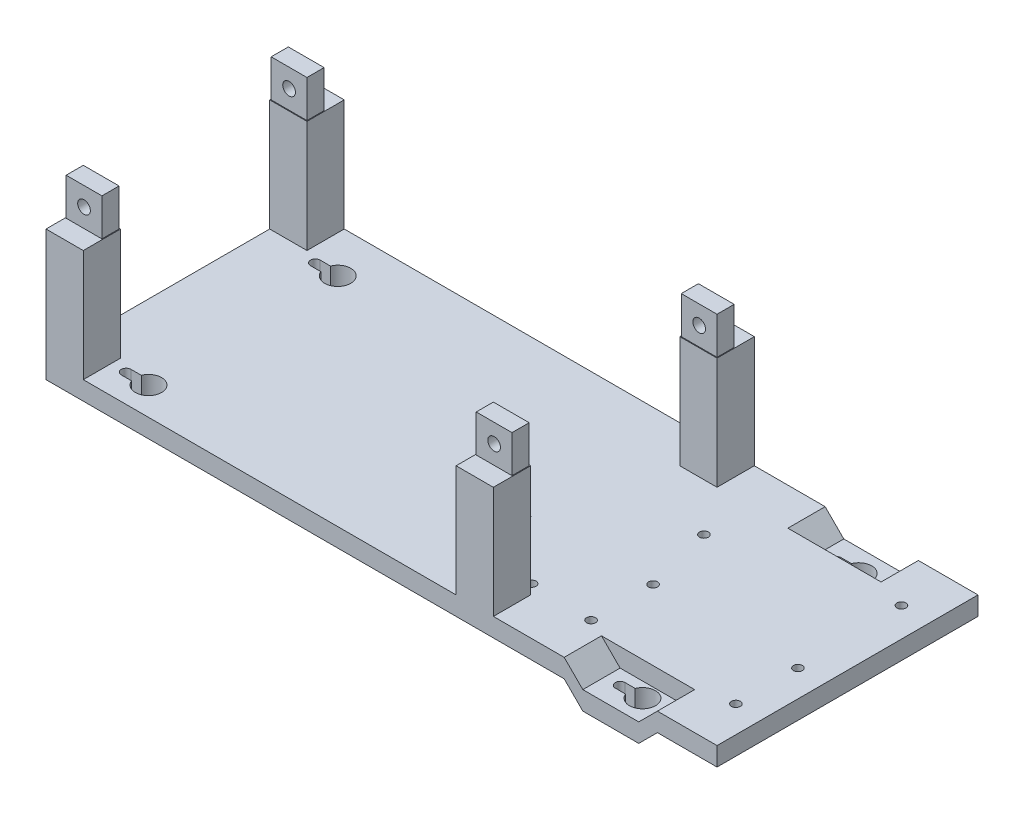
SolidWorks part; units mm, degrees
ref_plane "Front Plane" through (0, 0, 0) normal (0, 0, 1) x (1, 0, 0)
ref_plane "Top Plane" through (0, 0, 0) normal (0, 1, 0) x (1, 0, 0)
ref_plane "Right Plane" through (0, 0, 0) normal (1, 0, 0) x (0, 0, -1)
sketch "Sketch1" plane through (0, 0, 0) normal (0, 1, 0) x (1, 0, 0)
  line L1 (-90, -35) -> (90, -35)
  line L2 (-90, -35) -> (-90, 35)
  line L3 (-90, 35) -> (90, 35)
  line L4 (90, -35) -> (90, 35)
  line L5 (-90, -35) -> (90, 35) construction
  line L6 (-90, 35) -> (90, -35) construction
  point P0 (0, 0)
  dimension "D1" = 180
  dimension "D2" = 70
extrude "Boss-Extrude1" add sketch "Sketch1" along normal blind 5
sketch "Sketch3" plane through (0, 5, 0) normal (0, 1, 0) x (1, 0, 0)
  line L0 (90, 35) -> (-90, 35) construction
  line L1 (69, 35) -> (54, 35)
  line L2 (69, 35) -> (69, 25)
  line L3 (69, 25) -> (54, 25)
  line L4 (54, 35) -> (54, 25)
  line L5 (-90, -35) -> (90, -35) construction
  line L6 (69, -35) -> (54, -35)
  line L7 (69, -35) -> (69, -25)
  line L8 (69, -25) -> (54, -25)
  line L9 (54, -35) -> (54, -25)
  line L10 (90, -35) -> (90, 35) construction
  dimension "D1" = 10
  dimension "D2" = 15
  dimension "D3" = 21
extrude "Cut-Extrude1" cut sketch "Sketch3" against normal blind 6
chamfer "Chamfer2" distance 5 angle 45 4 edges at (54, 5, 30) (69, 5, 30) (69, 5, -30) (54, 5, -30)
sketch "Sketch5" plane through (0, 0, 0) normal (0, -1, 0) x (1, 0, 0)
  line L0 (-90, 35) -> (54, 35) construction
  line L1 (49, 35) -> (74, 35)
  line L2 (49, 35) -> (49, 23)
  line L3 (49, 23) -> (74, 23)
  line L4 (74, 35) -> (74, 23)
  line L5 (54, -35) -> (-90, -35) construction
  line L6 (49, -35) -> (74, -35)
  line L7 (49, -35) -> (49, -23)
  line L8 (49, -23) -> (74, -23)
  line L9 (74, -35) -> (74, -23)
  line L10 (74, 25) -> (74, 35) construction
  line L11 (49, 35) -> (49, 25) construction
  dimension "D1" = 12
extrude "Boss-Extrude7" add sketch "Sketch5" along normal blind 5
chamfer "Chamfer4" distance 5 angle 45 4 edges at (49, -5, 29) (74, -5, 29) (74, -5, -29) (49, -5, -29)
sketch "Sketch6" plane through (0, 0, 0) normal (0, 1, 0) x (1, 0, 0)
  line L0 (58, -29) -> (64, -29) construction
  line L1 (58, -27.7) -> (64, -27.7)
  line L2 (58, -30.3) -> (64, -30.3)
  line L3 (69, -35) -> (54, -35) construction
  line L5 (58, 29) -> (64, 29) construction
  line L6 (58, 30.3) -> (64, 30.3)
  line L7 (58, 27.7) -> (64, 27.7)
  line L8 (54, 35) -> (69, 35) construction
  line L9 (69, -25) -> (69, -35) construction
  circle A0 centre (64, -29) radius 3.5
  arc A1 (58, -27.7) -> (58, -30.3) centre (58, -29) ccw
  arc A2 (64, -30.3) -> (64, -27.7) centre (64, -29) ccw
  circle A3 centre (64, 29) radius 3.5
  arc A4 (58, 30.3) -> (58, 27.7) centre (58, 29) ccw
  arc A5 (64, 27.7) -> (64, 30.3) centre (64, 29) ccw
  point P2 (61, -29)
  point P15 (61, 29)
  dimension "D1" = 7
  dimension "D2" = 2.6
  dimension "D3" = 6
  dimension "D4" = 5
  dimension "D5" = 6
  dimension "D6" = 6
extrude "Cut-Extrude2" cut sketch "Sketch6" against normal through all contours A4 L6 A0 L7 | L6 A4 L7 A0 | L7 A5 L6 A0 | L1 A1 L2 | L2 A2 L1 | A2 L2 A0 L1 region at (58.7697, 0, 29) region at (64.6436, 0, 25.6587) region at (62.8105, 0, 29) region at (58.7697, 0, -29) region at (64.6436, 0, -32.3413) region at (62.8105, 0, -29)
sketch "Sketch7" plane through (0, 5, 0) normal (0, 1, 0) x (1, 0, 0)
  line L0 (-76, -27.5) -> (-70, -27.5) construction
  line L1 (-76, -26.2) -> (-70, -26.2)
  line L2 (-76, -28.8) -> (-70, -28.8)
  line L4 (-90, -35) -> (49, -35) construction
  line L5 (-90, 35) -> (-90, -35) construction
  line L6 (-76, 23.25) -> (-70, 23.25) construction
  line L7 (-76, 24.55) -> (-70, 24.55)
  line L8 (-76, 21.95) -> (-70, 21.95)
  circle A0 centre (-70, -27.5) radius 3.5
  arc A1 (-76, -26.2) -> (-76, -28.8) centre (-76, -27.5) ccw
  arc A2 (-70, -28.8) -> (-70, -26.2) centre (-70, -27.5) ccw
  circle A3 centre (-70, 23.25) radius 3.5
  arc A4 (-76, 24.55) -> (-76, 21.95) centre (-76, 23.25) ccw
  arc A5 (-70, 21.95) -> (-70, 24.55) centre (-70, 23.25) ccw
  point P3 (-73, -27.5)
  point P14 (-73, 23.25)
  dimension "D3" = 7
  dimension "D6" = 50.75
  dimension "D1" = 6
  dimension "D2" = 2.6
  dimension "D4" = 7.5
  dimension "D5" = 20
extrude "Cut-Extrude3" cut sketch "Sketch7" against normal through all contours A2 L2 A0 L1 | A5 L8 A3 L7 | L1 A2 L2 A1 | L8 A5 L7 A4 region at (-69.3564, 5, 24.1587) region at (-69.3564, 5, -26.5913)
sketch "Sketch8" plane through (0, 5, 0) normal (0, 1, 0) x (1, 0, 0)
  line L1 (-90, -35) -> (-80, -35)
  line L2 (-90, -35) -> (-90, -25)
  line L3 (-90, -25) -> (-80, -25)
  line L4 (-80, -35) -> (-80, -25)
  line L5 (-90, 35) -> (-80, 35)
  line L6 (-90, 35) -> (-90, 25)
  line L7 (-90, 25) -> (-80, 25)
  line L8 (-80, 35) -> (-80, 25)
  line L9 (30, -35) -> (20, -35)
  line L10 (30, -35) -> (30, -25)
  line L11 (30, -25) -> (20, -25)
  line L12 (20, -35) -> (20, -25)
  line L13 (30, 35) -> (20, 35)
  line L14 (30, 35) -> (30, 25)
  line L15 (30, 25) -> (20, 25)
  line L16 (20, 35) -> (20, 25)
  dimension "D1" = 10
  dimension "D2" = 10
  dimension "D3" = 120
extrude "Boss-Extrude8" add sketch "Sketch8" along normal blind 40
sketch "Sketch9" plane through (0, 45, 0) normal (0, 1, 0) x (1, 0, 0)
  line L1 (20, 35) -> (20, 25) construction
  line L2 (30, 35) -> (20, 35)
  line L3 (30, 35) -> (30, 30)
  line L4 (30, 30) -> (20, 30)
  line L5 (20, 35) -> (20, 30)
  line L6 (-90, 35) -> (-90, 25) construction
  line L8 (-80, 35) -> (-90, 35)
  line L9 (-80, 35) -> (-80, 30)
  line L10 (-80, 30) -> (-90, 30)
  line L11 (-90, 35) -> (-90, 30)
  line L12 (-90, -25) -> (-90, -35) construction
  line L14 (-80, -35) -> (-90, -35)
  line L15 (-80, -35) -> (-80, -30)
  line L16 (-80, -30) -> (-90, -30)
  line L17 (-90, -35) -> (-90, -30)
  line L18 (20, -25) -> (20, -35) construction
  line L20 (30, -35) -> (20, -35)
  line L21 (30, -35) -> (30, -30)
  line L22 (30, -30) -> (20, -30)
  line L23 (20, -35) -> (20, -30)
  line L57 (-90, 30) -> (-89.9, 30)
  line M1 (30, 25) -> (30, 35)
  line M2 (30, 35) -> (20, 35)
  line M3 (20, 35) -> (20, 25)
extrude "Cut-Extrude4" cut sketch "Sketch9" against normal blind 10 contours L10 | L10 | L22 | L22 | L16 | L16 | L23 L20 L21 L22 | L4 M1 M2 M3 | L8 L11 L10 L9 | L17 L14 L15 L16 region at (25, 45, -32.5) region at (-85, 45, -32.5) region at (-85, 45, 32.5) region at (25, 45, 32.5)
hole_wizard "M3 Clearance Hole2" positions "Sketch13" profile "Sketch12" hole size "M3" standard "ANSI Metric" end condition through all
sketch "Sketch13" plane through (0, 0, -35) normal (0, 0, -1) x (-1, 0, 0)
  line L0 (-20, 35) -> (-20, 5) construction
  line L1 (-30, 45) -> (-20, 45) construction
  line L2 (80, 35) -> (80, 5) construction
  point P0 (-25, 40)
  point P2 (85, 40)
  dimension "D1" = 5
  dimension "D2" = 5
  dimension "D3" = 5
sketch "Sketch12" plane through (25, 40, -35) normal (1, 0, 0) x (0, 1, 0)
  line L0 (0, 0) -> (0, 70.0001)
  line L1 (0, 70.0001) -> (1.7, 70.0001)
  line L2 (1.7, 70.0001) -> (1.7, 0)
  line L5 (1.7, 0) -> (0, 0)
  line L11 (0, -6.35) -> (0, 107.95) construction
  dimension "Thru Hole Dia." = 3.4
  dimension "Thru Hole Depth" = 70.0001
hole_wizard "M2 Clearance Hole1" positions "Sketch15" profile "Sketch14" hole size "M2" standard "ANSI Metric"
sketch "Sketch15" plane through (0, 5, 0) normal (0, 1, 0) x (1, 0, 0)
  circle A0 centre (11.0135, -7.6645) radius 1.0414 construction
  circle A1 centre (27.5235, -22.2695) radius 1.0414 construction
  circle A2 centre (43.979, -22.7775) radius 1.0922 construction
  circle A3 centre (43.979, -6.1405) radius 1.0922 construction
  circle A4 centre (82.841, -22.7775) radius 1.0922 construction
  circle A5 centre (82.841, -6.1405) radius 1.0922 construction
  circle A7 centre (39.235, 12.25) radius 1.0922 construction
  point P0 (43.979, -22.7775)
  point P2 (43.979, -6.1405)
  point P4 (82.841, -6.1405)
  point P6 (82.841, -22.7775)
  point P8 (82.1869, 22.2793)
  point P10 (39.235, 12.25)
  point P12 (27.5235, -22.2695)
  point P14 (11.0135, -7.6645)
sketch "Sketch14" plane through (43.979, 5, 22.7775) normal (1, 0, 0) x (0, 0, 1)
  line L0 (0, 0) -> (0, 65.741)
  line L1 (0, 65.741) -> (1.2, 65.02)
  line L2 (1.2, 65.02) -> (1.2, 0)
  line L5 (1.2, 0) -> (0, 0)
  line L10 (0, 65.741) -> (-1.2, 65.02) construction
  line L11 (0, -6.35) -> (0, 107.95) construction
  dimension "Hole Dia." = 2.4
  dimension "Hole Depth" = 65.02
  dimension "Drill Angle" = 118
sketch "Sketch16" plane through (0, 45, 0) normal (0, 1, 0) x (1, 0, 0)
  line L18 (20.2, 29.8) -> (20.2, 25.2)
  line L19 (29.8, 29.8) -> (20.2, 29.8)
  line L20 (20.2, 25.2) -> (29.8, 25.2)
  line L21 (29.8, 25.2) -> (29.8, 29.8)
  line L22 (20.2, 29.8) -> (20.2, 25.2)
  line L23 (29.8, 29.8) -> (20.2, 29.8)
  line L24 (20.2, 25.2) -> (29.8, 25.2)
  line L25 (29.8, 25.2) -> (29.8, 29.8)
  line L46 (-80.2, 29.8) -> (-89.8, 29.8)
  line L47 (-89.8, 29.8) -> (-89.8, 25.2)
  line L48 (-89.8, 25.2) -> (-80.2, 25.2)
  line L49 (-80.2, 25.2) -> (-80.2, 29.8)
  line L50 (-80.2, 29.8) -> (-89.8, 29.8)
  line L51 (-89.8, 29.8) -> (-89.8, 25.2)
  line L52 (-89.8, 25.2) -> (-80.2, 25.2)
  line L53 (-80.2, 25.2) -> (-80.2, 29.8)
  line L64 (-80.2, -25.2) -> (-89.8, -25.2)
  line L65 (-89.8, -25.2) -> (-89.8, -29.8)
  line L66 (-89.8, -29.8) -> (-80.2, -29.8)
  line L67 (-80.2, -29.8) -> (-80.2, -25.2)
  line L68 (-80.2, -25.2) -> (-89.8, -25.2)
  line L69 (-89.8, -25.2) -> (-89.8, -29.8)
  line L70 (-89.8, -29.8) -> (-80.2, -29.8)
  line L71 (-80.2, -29.8) -> (-80.2, -25.2)
  line L117 (20.2, -25.2) -> (20.2, -29.8)
  line L118 (20.2, -29.8) -> (29.8, -29.8)
  line L119 (29.8, -29.8) -> (29.8, -25.2)
  line L120 (29.8, -25.2) -> (20.2, -25.2)
  line L121 (20.2, -25.2) -> (20.2, -29.8)
  line L122 (20.2, -29.8) -> (29.8, -29.8)
  line L123 (29.8, -29.8) -> (29.8, -25.2)
  line L124 (29.8, -25.2) -> (20.2, -25.2)
  dimension "D1" = 0.2
  dimension "D2" = 0.2
  dimension "D3" = 0.2
  dimension "D4" = 0.2
extrude "Cut-Extrude5" cut sketch "Sketch16" against normal blind 10 flip side to cut
equation "\"D6@Sketch6\"=\"D3@Sketch6\""
equation "\"D3@Sketch13\"=\"D1@Sketch13\""
equation "\"D2@Sketch16\"=\"D1@Sketch16\""
equation "\"D3@Sketch16\"=\"D1@Sketch16\""
equation "\"D4@Sketch16\"=\"D1@Sketch16\""
